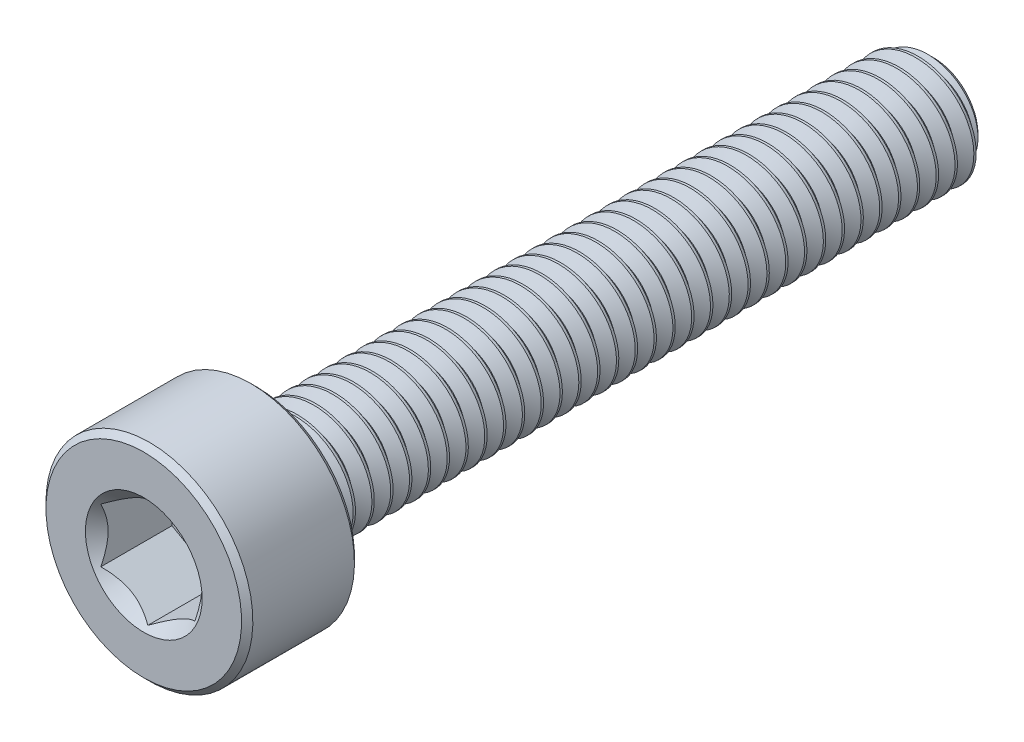
SolidWorks part; units mm, degrees
ref_plane "Front Plane" through (0, 0, 0) normal (0, 0, 1) x (1, 0, 0)
ref_plane "Top Plane" through (0, 0, 0) normal (0, 1, 0) x (1, 0, 0)
ref_plane "Right Plane" through (0, 0, 0) normal (1, 0, 0) x (0, 0, -1)
sketch "Sketch1" plane through (0, 0, 0) normal (1, 0, 0) x (0, 0, -1)
  line L0 (-10.5, 0) -> (10.5, 0) construction
  line L1 (10.5, 0) -> (10.5, 1.1752) construction
  line L2 (10.5, 1.1752) -> (10.1752, 1.5) construction
  line L3 (10.1752, 1.5) -> (10.125, 1.5) construction
  line L4 (10.125, 1.5) -> (-7.5, 1.5) construction
  line L5 (-7.5, 1.5) -> (-7.5, 2.75) construction
  line L6 (-7.5, 2.75) -> (-10.5, 2.75) construction
  line L7 (-10.5, 2.75) -> (-10.5, 0) construction
  line L8 (10.5, 1.1752) -> (10.5, 1.5) construction
  line L9 (10.4688, 1.5541) -> (10.7188, 1.1211) construction
  line L10 (10.7188, 1.1211) -> (10.9688, 1.5541) construction
  line L11 (10.9688, 1.5541) -> (10.4688, 1.5541) construction
  line L12 (10.7188, 1.5541) -> (10.7188, 1.5) construction
  line L13 (10.7188, 1.1211) -> (10.7188, 1.1752) construction
  line L14 (10.6875, 1.1752) -> (10.75, 1.1752) construction
  line L15 (10.5, 1.5) -> (10.9375, 1.5) construction
  line L16 (10.4844, 1.5271) -> (10.9531, 1.5271) construction
  line L17 (10.5, 0) -> (10.5, -1.5) construction
  line L18 (-7.65, 2.75) -> (-7.5, 2.6) construction
  line L19 (-10.35, 2.75) -> (-10.5, 2.6) construction
  line L20 (-7.5, 1.5) -> (-7.5, 0) construction
  line L21 (-7.5, 0.75) -> (-1.5, 0.75) construction
  line L22 (-1.5, 0.75) -> (4.5, 0.75) construction
  line L23 (4.5, 0.75) -> (10.5, 0.75) construction
  line L24 (-1.5, 0.75) -> (-1.5, 1.5) construction
  line L25 (-1.5, 1.5) -> (-1.5, 2.75) construction
  line L26 (4.5, 0.75) -> (4.5, 2.75) construction
  point P0 (-10.5, 1.25)
  point P3 (9.25, 1.5)
  point P4 (0, 0)
  point P18 (4.5, 1.5)
  point P22 (10.7188, 1.1752)
  point P24 (10.125, 1.5)
  point P25 (10.7188, 1.5)
  point P28 (10.7188, 1.5271)
  point P29 (9.25, -1.5)
  point P30 (-1.5, 1.5)
  point P31 (-9, 2.75)
  point P37 (-8.025, 2.75)
  point P38 (-10.275, 2.75)
  point P45 (-1.5, 0.75)
  point P46 (4.5, 0.75)
  dimension "D2" = 0.0625
  dimension "D7" = 0.15
  dimension "D8" = 0.15
  dimension "D9" = 0.15
  dimension "D10" = 0.075
  dimension "D11" = 0.375
  dimension "Drive Size" = 2.5
  dimension "Head Diameter" = 5.5
  dimension "Head Height" = 3
  dimension "Thread Pitch" = 0.5
  dimension "Thread Dia" = 3
  dimension "Length" = 18
  dimension "D12" = 0.375
  dimension "D4" = 1.25
  dimension "D3" = 45
sketch "Sketch2" plane through (0, 0, 0) normal (1, 0, 0) x (0, 0, -1)
  line L0 (-10.5, 0) -> (-10.5, 2.6)
  line L1 (-10.35, 2.75) -> (-7.65, 2.75)
  line L2 (-7.5, 2.6) -> (-7.5, 1.65)
  line L4 (10.1752, 1.5) -> (10.5, 1.1752)
  line L5 (10.5, 1.1752) -> (10.5, 0)
  line L6 (-7.5, 2.75) -> (-10.5, 2.75) construction
  line L7 (10.5, 0) -> (-10.5, 0)
  line L8 (-10.35, 2.75) -> (-10.5, 2.6) construction
  line L10 (-10.35, 2.75) -> (-10.5, 2.6)
  line L14 (-7.65, 2.75) -> (-7.5, 2.6) construction
  line L16 (-7.65, 2.75) -> (-7.5, 2.6)
  line L17 (-7.5, 1.5) -> (-7.5, 2.75) construction
  line L19 (-7.35, 1.5) -> (10.1752, 1.5)
  line L20 (10.125, 1.5) -> (-7.5, 1.5) construction
  arc A1 (-7.5, 1.65) -> (-7.35, 1.5) centre (-7.35, 1.65) ccw
  dimension "D3" = 0.15
revolve "Revolve1" add sketch "Sketch2" angle 360 about L7
sketch "Sketch3" plane through (0, 0, 10.5) normal (0, 0, 1) x (1, 0, 0)
  line L1 (1.25, -0.7217) -> (1.25, 0.7217)
  line L2 (1.25, 0.7217) -> (0, 1.4434)
  line L3 (0, 1.4434) -> (-1.25, 0.7217)
  line L4 (-1.25, 0.7217) -> (-1.25, -0.7217)
  line L5 (-1.25, -0.7217) -> (0, -1.4434)
  line L6 (0, -1.4434) -> (1.25, -0.7217)
  circle A0 centre (0, 0) radius 1.25 construction
  circle A1 centre (0, 0) radius 2.75 construction
  circle A2 centre (0, 0) radius 2.75 construction
  circle A3 centre (0, 0) radius 1.4434 construction
  point P13 (0, 0)
  dimension "D1" = 2.8868
extrude "Cut-Extrude1" cut sketch "Sketch3" against normal offset from surface (2 mm away) 1 up to face at (0, 2.6, 7.5)
sketch "Sketch4" plane through (0, 0, 10.5) normal (0, 0, 1) x (1, 0, 0)
  circle A0 centre (0, 0) radius 1.5516
  dimension "D1" = 3.1033
extrude "Cut-Extrude2" cut sketch "Sketch4" against normal up to vertex (1.5 mm away) draft 45 up to point (0, 2.75, 9)
sketch "Sketch11" plane through (0, 0, 0) normal (1, 0, 0) x (0, 0, -1)
  line L0 (-10.5, 0) -> (10.5, 0) construction
  line L1 (-10.5, 0) -> (10.5, 0) construction
  line L2 (-4.125, 0) -> (-4.125, 1.5) construction
  line L3 (10.125, 1.5) -> (-7.5, 1.5) construction
  line L4 (7.125, 0) -> (7.125, 1.5) construction
  line L6 (10.5, 1.1752) -> (10.5, 1.5) construction
  point P2 (-4.125, 0)
  point P3 (7.125, 0)
  dimension "D1" = 3.375
  dimension "D2" = 3.375
sketch "Sketch6" plane through (0, 0, -10.5) normal (0, 0, -1) x (-1, 0, 0)
  circle A0 centre (0, 0) radius 1.5
curve "Helix/Spiral1" pitch 0.5 height 18.5 radius 1.5 centre (0, 0, -10.5) axis (0, 0, 1) start towards (0, 1, 0)
sketch "Sketch10" plane through (0, 0, 0) normal (1, 0, 0) x (0, 0, -1)
  line L0 (-7.35, -2.75) -> (-7.35, 2.75)
  line L5 (-10.5, 0) -> (10.5, 0) construction
  line L6 (-7.35, 1.5) -> (-7.35, -1.5) construction
  point P3 (-7.35, 0)
split "Split1" trim tools "Sketch10" bodies to split 106 resulting bodies 114 115
sketch "Sketch7" plane through (0, 0, 0) normal (1, 0, 0) x (0, 0, -1)
  line L0 (10.4844, 1.5271) -> (10.9531, 1.5271)
  line L1 (10.9531, 1.5271) -> (10.75, 1.1752)
  line L2 (10.75, 1.1752) -> (10.6875, 1.1752)
  line L3 (10.6875, 1.1752) -> (10.4844, 1.5271)
sweep "Cut-Sweep1" cut profiles "Sketch7" path "Helix/Spiral1" align with end faces yes
sketch "Sketch8" plane through (0, 0, 0) normal (1, 0, 0) x (0, 0, -1)
  line L0 (-7.5, 0) -> (-7.5, 1.5)
  line L1 (-7.35, -1.5) -> (-7.35, 1.5) construction
  line L2 (-7.5, 1.5) -> (-7.35, 1.5)
  line L4 (-7.35, 1.5) -> (-6.484, 0)
  line L5 (-6.484, 0) -> (-7.5, 0)
  line L6 (10.125, 1.5) -> (-7.5, 1.5) construction
  line L7 (-10.5, 0) -> (10.5, 0) construction
  dimension "D1" = 60
revolve "Revolve2" add sketch "Sketch8" angle 360 about L5
equation "\"D2@Sketch1\" = \"Thread Pitch@Sketch1\" / 8"
equation "\"D4@Helix/Spiral1\" = \"Thread Pitch@Sketch1\""
equation "\"D7@Sketch1\" = \"Head Height@Sketch1\" * .05"
equation "\"D8@Sketch1\"=\"D7@Sketch1\""
equation "\"D9@Sketch1\"=\"D7@Sketch1\""
equation "\"D10@Sketch1\"=\"D7@Sketch1\"/2"
equation "\"D11@Sketch1\"=\"D10@Sketch1\"*5"
equation "\"D4@Sketch1\"=\"Thread Pitch@Sketch1\"*2.5"
equation "\"D12@Sketch1\"=\"Thread Pitch@Sketch1\"*.75"
equation "\"D3@Helix/Spiral1\"=\"Length@Sketch1\"+\"Thread Pitch@Sketch1\""
equation "\"D3@Sketch2\"=\"Thread Dia@Sketch1\"*0.05"
equation "\"D1@Sketch11\"=\"Length@Sketch1\"*0.1875"
equation "\"D2@Sketch11\"=\"D1@Sketch11\""
equation "\"D1@Sketch4\"=\"D1@Sketch3\"*1.075"
